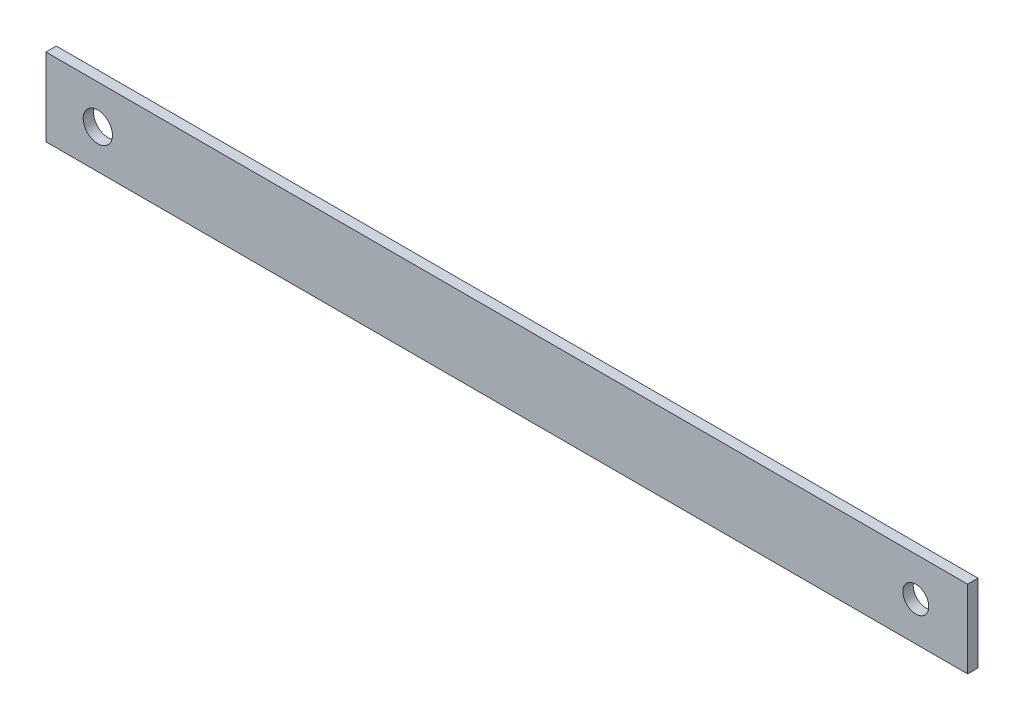
SolidWorks part; units mm, degrees
ref_plane "Front Plane" through (0, 0, 0) normal (0, 0, 1) x (1, 0, 0)
ref_plane "Top Plane" through (0, 0, 0) normal (0, 1, 0) x (1, 0, 0)
ref_plane "Right Plane" through (0, 0, 0) normal (1, 0, 0) x (0, 0, -1)
sketch "Sketch1" plane through (0, 0, 0) normal (0, 0, 1) x (1, 0, 0)
  line L1 (0, 0) -> (177.8, 0)
  line L2 (0, 0) -> (0, 15)
  line L3 (0, 15) -> (177.8, 15)
  line L4 (177.8, 0) -> (177.8, 15)
  dimension "D1" = 15
  dimension "D2" = 177.8
base flange "Base-Flange1" sketch "Sketch1" thickness 2 reverse thickness direction no parameters "D1"=0.7366
sketch "Sketch6" plane through (0, 0, 0) normal (0, 0, 1) x (1, 0, 0)
  line L0 (0, 15) -> (0, 0) construction
  line L1 (177.8, 0) -> (177.8, 15) construction
  line L2 (0, 0) -> (177.8, 0) construction
  circle A0 centre (10, 7.5) radius 2.8237
  circle A1 centre (167.8, 7.5) radius 2.5
  dimension "D3" = 5
  dimension "D4" = 5.6473
  dimension "D1" = 10
  dimension "D2" = 10
  dimension "D5" = 7.5
extrude "Cut-Extrude1" cut sketch "Sketch6" against normal up to next normal cut yes
sketch "Sketch7" [suppressed] plane through (0, 0, 0) normal (0, 0, 1) x (1, 0, 0)
  line L0 (200, 15) -> (0, 15) construction
  line L1 (200, 0) -> (185, 0)
  line L2 (200, 0) -> (200, 15)
  line L3 (200, 15) -> (185, 15)
  line L4 (185, 0) -> (185, 15)
  line L5 (0, 0) -> (200, 0) construction
  circle A0 centre (175, 7.5) radius 2.5
  dimension "D4" = 5
  dimension "D1" = 30
  dimension "D2" = 7.5
  dimension "D3" = 10
extrude "Cut-Extrude2" [suppressed] cut sketch "Sketch7" against normal up to next
sketch "Bend-Lines1" plane through (0, 0, 0) normal (0, 1, 0) x (1, 0, 0)
sketch "Bounding-Box1" plane through (0, 0, 0) normal (0, 1, 0) x (1, 0, 0)
sheet metal parameters "Sheet-Metal1" thickness 2 parameters "D1"=0.7366
flat pattern "Flat-Pattern1" [suppressed]
sketch "Bend-Lines2" plane through (0, 0, 0) normal (0, 1, 0) x (1, 0, 0)
sketch "Bounding-Box2" [suppressed] plane through (0, 0, 0) normal (0, 1, 0) x (1, 0, 0)
sheet metal parameters "Sheet-Metal2" thickness 2 parameters "D1"=0.7366
flat pattern "Flat-Pattern1"
sketch "Bend-Lines2" plane through (0, 0, 0) normal (0, 1, 0) x (1, 0, 0)
sketch "Bounding-Box2" [suppressed] plane through (0, 0, 0) normal (0, 1, 0) x (1, 0, 0)
sheet metal parameters "Sheet-Metal3" [suppressed] thickness 2 parameters "D1"=0.7366
flat pattern "Flat-Pattern1"
sketch "Bend-Lines2" plane through (0, 0, 0) normal (0, 1, 0) x (1, 0, 0)
sketch "Bounding-Box2" [suppressed] plane through (0, 0, 0) normal (0, 1, 0) x (1, 0, 0)
